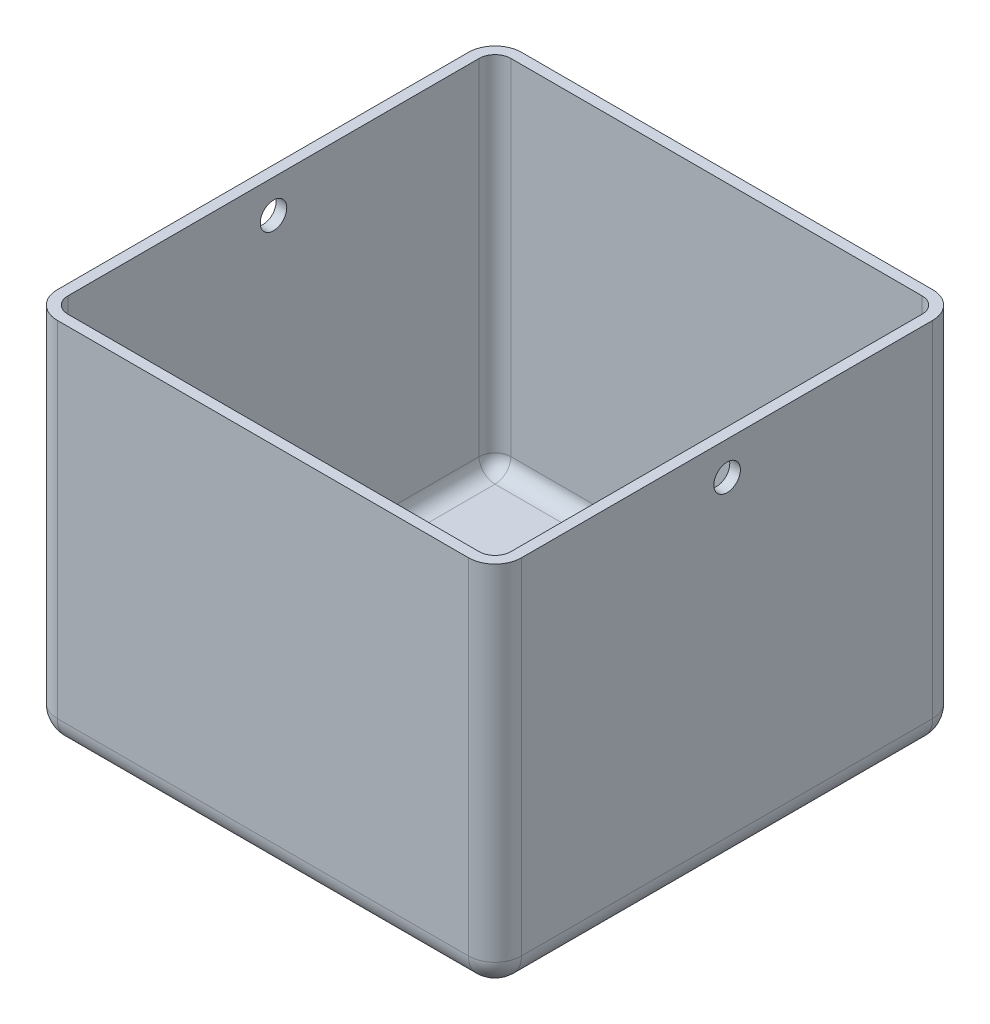
SolidWorks part; units mm, degrees
ref_plane "Front Plane" through (0, 0, 0) normal (0, 0, 1) x (1, 0, 0)
ref_plane "Top Plane" through (0, 0, 0) normal (0, 1, 0) x (1, 0, 0)
ref_plane "Right Plane" through (0, 0, 0) normal (1, 0, 0) x (0, 0, -1)
sketch "Sketch1" plane through (0, 0, 0) normal (0, 1, 0) x (1, 0, 0)
  line L1 (-35, -35) -> (35, -35)
  line L2 (-35, -35) -> (-35, 35)
  line L3 (-35, 35) -> (35, 35)
  line L4 (35, -35) -> (35, 35)
  line L5 (-35, -35) -> (35, 35) construction
  line L6 (-35, 35) -> (35, -35) construction
  point P0 (0, 0)
  dimension "D1" = 70
  dimension "D2" = 70
extrude "Boss-Extrude1" add sketch "Sketch1" along normal blind 56
fillet "Fillet1" radius 4 8 edges at (-35, 0, 0) (0, 0, -35) (35, 0, 0) (0, 0, 35) (-35, 28, -35) (-35, 28, 35) (35, 28, -35) (35, 28, 35)
shell "Shell1" thickness 1.6 removed face at (0, 56, 0)
sketch "Sketch2" plane through (0, 1.6, 0) normal (0, 1, 0) x (1, 0, 0)
  line L28 (18.8649, 1.6027) -> (12.7611, 8.2248)
  line L29 (8.3493, 10.1583) -> (-8.2959, 10.1583)
  line L30 (-12.7077, 8.2248) -> (-18.8115, 1.6027)
  line L31 (-12.7077, -8.4082) -> (-18.8115, -1.7861)
  line L32 (8.3493, -10.3417) -> (-8.2959, -10.3417)
  line L33 (18.8649, -1.7861) -> (12.7611, -8.4082)
  line L34 (20.3355, 2.9582) -> (14.2317, 9.5803)
  line L35 (8.3493, 12.1583) -> (-8.2959, 12.1583)
  line L36 (-14.1783, 9.5803) -> (-20.2821, 2.9582)
  line L37 (-14.1783, -9.7637) -> (-20.2821, -3.1416)
  line L38 (8.3493, -12.3417) -> (-8.2959, -12.3417)
  line L39 (20.3355, -3.1416) -> (14.2317, -9.7637)
  arc A20 (12.7611, 8.2248) -> (8.3493, 10.1583) centre (8.3493, 4.1583) ccw
  arc A21 (-8.2959, 10.1583) -> (-12.7077, 8.2248) centre (-8.2959, 4.1583) ccw
  arc A22 (-18.8115, 1.6027) -> (-18.8115, -1.7861) centre (-16.9733, -0.0917) ccw
  arc A23 (-8.2959, -10.3417) -> (-12.7077, -8.4082) centre (-8.2959, -4.3417) cw
  arc A24 (12.7611, -8.4082) -> (8.3493, -10.3417) centre (8.3493, -4.3417) cw
  arc A25 (18.8649, 1.6027) -> (18.8649, -1.7861) centre (17.0267, -0.0917) cw
  arc A26 (14.2317, 9.5803) -> (8.3493, 12.1583) centre (8.3493, 4.1583) ccw
  arc A27 (-8.2959, 12.1583) -> (-14.1783, 9.5803) centre (-8.2959, 4.1583) ccw
  arc A28 (-20.2821, 2.9582) -> (-20.2821, -3.1416) centre (-16.9733, -0.0917) ccw
  arc A29 (-8.2959, -12.3417) -> (-14.1783, -9.7637) centre (-8.2959, -4.3417) cw
  arc A30 (14.2317, -9.7637) -> (8.3493, -12.3417) centre (8.3493, -4.3417) cw
  arc A31 (20.3355, 2.9582) -> (20.3355, -3.1416) centre (17.0267, -0.0917) cw
  dimension "D1" = 2
extrude "Cut-Extrude1" cut sketch "Sketch2" against normal through all contours L28 A20 L29 A21 L30 A22 L31 A23 L32 A24 L33 A25
extrude "Boss-Extrude2" add sketch "Sketch2<4>" along normal blind 8
sketch "Sketch2<4>" plane through (0, 1.6, 0) normal (0, 1, 0) x (1, 0, 0) same geometry as "Sketch2"
sketch "Sketch3" plane through (0, 0, -12.1583) normal (0, 0, -1) x (-1, 0, 0)
  line L0 (-0.0267, 9.6) -> (-0.0267, 1.6) construction
  line L1 (-8.3493, 9.6) -> (8.2959, 9.6) construction
  circle A0 centre (-0.0267, 5.6) radius 2.4
extrude "Cut-Extrude2" cut sketch "Sketch3" against normal up to surface (24.5 mm away) up to face at (0.0267, 5.6, 12.3417)
sketch "Sketch4" plane through (35, 0, 0) normal (1, 0, 0) x (0, 0, -1)
  line L0 (0, 56) -> (0, 46)
  line L1 (0, 55.3) -> (-3.7239, 53.15)
  line L2 (-3.7239, 53.15) -> (-3.7239, 48.85)
  line L3 (-3.7239, 48.85) -> (0, 46.7)
  line L4 (0, 46.7) -> (3.7239, 48.85)
  line L5 (3.7239, 48.85) -> (3.7239, 53.15)
  line L6 (3.7239, 53.15) -> (0, 55.3)
  line L7 (31, 56) -> (-31, 56)
  line L8 (0, 56) -> (0, 62.3252)
  circle A0 centre (0, 51) radius 4.3 construction
  circle A1 centre (0, 51) radius 2
extrude "Cut-Extrude3" cut sketch "Sketch4" against normal up to surface (70 mm away) contours L0 A1 | L0 A1 region at (35, 51, -0.8488) region at (35, 51, 0.8488) up to face at (-35, 30, 0)
sketch "Sketch5" plane through (0, 0, 33.4) normal (0, 0, -1) x (-1, 0, 0)
  line L0 (0, 50.2) -> (0, -1.8)
  line L1 (31, 56) -> (-31, 56) construction
  line L2 (0.7, 14) -> (0.7, 32.8)
  line L3 (2.3, 15.6) -> (28.7, 15.6)
  line L4 (2.3, 15.6) -> (2.3, 32.8)
  line L5 (2.3, 32.8) -> (28.7, 32.8)
  line L6 (28.7, 15.6) -> (28.7, 32.8)
  line L7 (2.3, 15.6) -> (28.7, 32.8) construction
  line L8 (2.3, 32.8) -> (28.7, 15.6) construction
  line L10 (30.3, 14) -> (30.3, 32.8)
  line L11 (0.7, 14) -> (30.3, 14)
  line L12 (2.3, 32.8) -> (0.7, 32.8)
  line L13 (28.7, 32.8) -> (30.3, 32.8)
  line L15 (-23.2, 32.8) -> (-23.2, 14)
  line L16 (-21.6, 32.8) -> (-8.4, 32.8)
  line L17 (0, 56) -> (31, 56)
  line L18 (15.5, 50.2) -> (15.5, -1.8)
  line L19 (-21.6, 32.8) -> (-21.6, 15.6)
  line L20 (-21.6, 15.6) -> (-8.4, 15.6)
  line L21 (-8.4, 32.8) -> (-8.4, 15.6)
  line L22 (-21.6, 32.8) -> (-8.4, 15.6) construction
  line L23 (-21.6, 15.6) -> (-8.4, 32.8) construction
  line L24 (-23.2, 14) -> (-6.8, 14)
  line L25 (-6.8, 32.8) -> (-6.8, 14)
  line L27 (-21.6, 32.8) -> (-23.2, 32.8)
  line L28 (-8.4, 32.8) -> (-6.8, 32.8)
  point P5 (15.5, 24.2)
  dimension "D1" = 26.4
  dimension "D2" = 17.2
  dimension "D3" = 13.2
  dimension "D4" = 17.2
extrude "Boss-Extrude3" add sketch "Sketch5" along normal blind 5.6 contours L28 L21 L20 L19 L27 L15 L24 L25 | L18 L3 L4 L12 L2 L11 | L3 L18 L11 L10 L13 L6 region at (-0.9393, 23.4, 33.4) region at (-15.7393, 14.8, 33.4) region at (22.4, 32.5505, 33.4)
sketch "Sketch6" plane through (21.6, 0, 0) normal (-1, 0, 0) x (0, 0, 1)
  line L0 (27.8, 15.6) -> (33.4, 15.6) construction
  line L1 (27.8, 32.8) -> (29.4, 32.8)
  line L2 (27.8, 32.8) -> (27.8, 15.6)
  line L3 (27.8, 15.6) -> (29.4, 15.6)
  line L4 (29.4, 32.8) -> (29.4, 15.6)
  dimension "D1" = 1.6
extrude "Boss-Extrude4" add sketch "Sketch6" along normal blind 1.6
sketch "Sketch7" plane through (8.4, 0, 0) normal (1, 0, 0) x (0, 0, -1)
  line L0 (-27.8, 15.6) -> (-33.4, 15.6) construction
  line L1 (-27.8, 32.8) -> (-29.4, 32.8)
  line L2 (-27.8, 32.8) -> (-27.8, 15.6)
  line L3 (-27.8, 15.6) -> (-29.4, 15.6)
  line L4 (-29.4, 32.8) -> (-29.4, 15.6)
  dimension "D1" = 1.6
extrude "Boss-Extrude5" add sketch "Sketch7" along normal blind 1.6
sketch "Sketch8" plane through (-2.3, 0, 0) normal (-1, 0, 0) x (0, 0, 1)
  line L0 (27.8, 15.6) -> (33.4, 15.6) construction
  line L1 (27.8, 32.8) -> (29.4, 32.8)
  line L2 (27.8, 32.8) -> (27.8, 15.6)
  line L3 (27.8, 15.6) -> (29.4, 15.6)
  line L4 (29.4, 32.8) -> (29.4, 15.6)
  dimension "D1" = 1.6
extrude "Boss-Extrude6" add sketch "Sketch8" along normal blind 1.6
sketch "Sketch9" plane through (-28.7, 0, 0) normal (1, 0, 0) x (0, 0, -1)
  line L0 (-27.8, 15.6) -> (-33.4, 15.6) construction
  line L1 (-27.8, 32.8) -> (-29.4, 32.8)
  line L2 (-27.8, 32.8) -> (-27.8, 15.6)
  line L3 (-27.8, 15.6) -> (-29.4, 15.6)
  line L4 (-29.4, 32.8) -> (-29.4, 15.6)
  dimension "D1" = 1.6
extrude "Boss-Extrude7" add sketch "Sketch9" along normal blind 1.6
sketch "Sketch10" plane through (0, 14, 0) normal (0, -1, 0) x (1, 0, 0)
  line L0 (-0.7, 27.8) -> (-30.3, 27.8) construction
  line L1 (23.2, 33.4) -> (6.8, 33.4)
  line L2 (23.2, 33.4) -> (23.2, 27.8)
  line L3 (23.2, 27.8) -> (6.8, 27.8)
  line L4 (6.8, 33.4) -> (6.8, 27.8)
  line L5 (-0.7, 33.4) -> (-30.3, 33.4)
  line L6 (-0.7, 33.4) -> (-0.7, 27.8)
  line L7 (-0.7, 27.8) -> (-30.3, 27.8)
  line L8 (-30.3, 33.4) -> (-30.3, 27.8)
  line L9 (-30.3, 27.8) -> (-30.3, 33.4) construction
extrude "Boss-Extrude8" add sketch "Sketch10" along normal up to next
